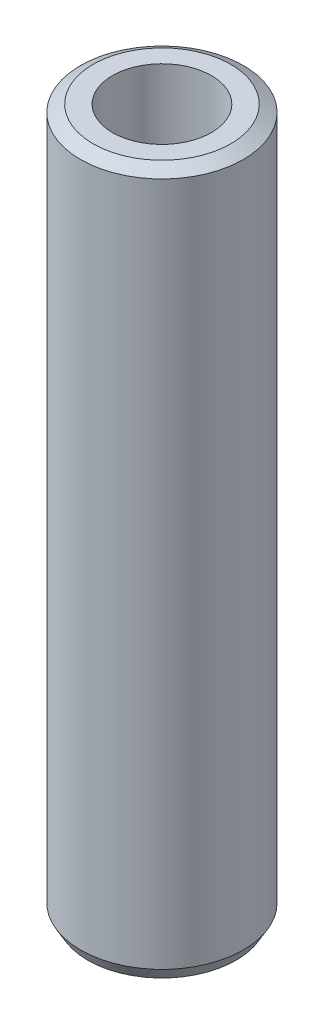
SolidWorks part; units mm, degrees
ref_plane "Front Plane" through (0, 0, 0) normal (0, 0, 1) x (1, 0, 0)
ref_plane "Top Plane" through (0, 0, 0) normal (0, 1, 0) x (1, 0, 0)
ref_plane "Right Plane" through (0, 0, 0) normal (1, 0, 0) x (0, 0, -1)
sketch "Sketch1" plane through (0, 0, 0) normal (0, 1, 0) x (1, 0, 0)
  circle A0 centre (0, 0) radius 20
  dimension "SHAFT_OD" = 40
extrude "Boss-Extrude1" add sketch "Sketch1" along normal blind 172.9854
sketch "Sketch2" plane through (0, 0, 0) normal (0, 1, 0) x (1, 0, 0)
  circle A0 centre (0, 0) radius 12.141
  dimension "BORE_D" = 24.282
extrude "Cut-Extrude1" cut sketch "Sketch2" along normal through all
chamfer "Chamfer1" distance 1.7884 angle 60 2 edges at (0, 172.9854, 20) (0, 0, 20) first distance on face at (0, 172.9854, 20) first distance on face at (0, 0, 12.141)
